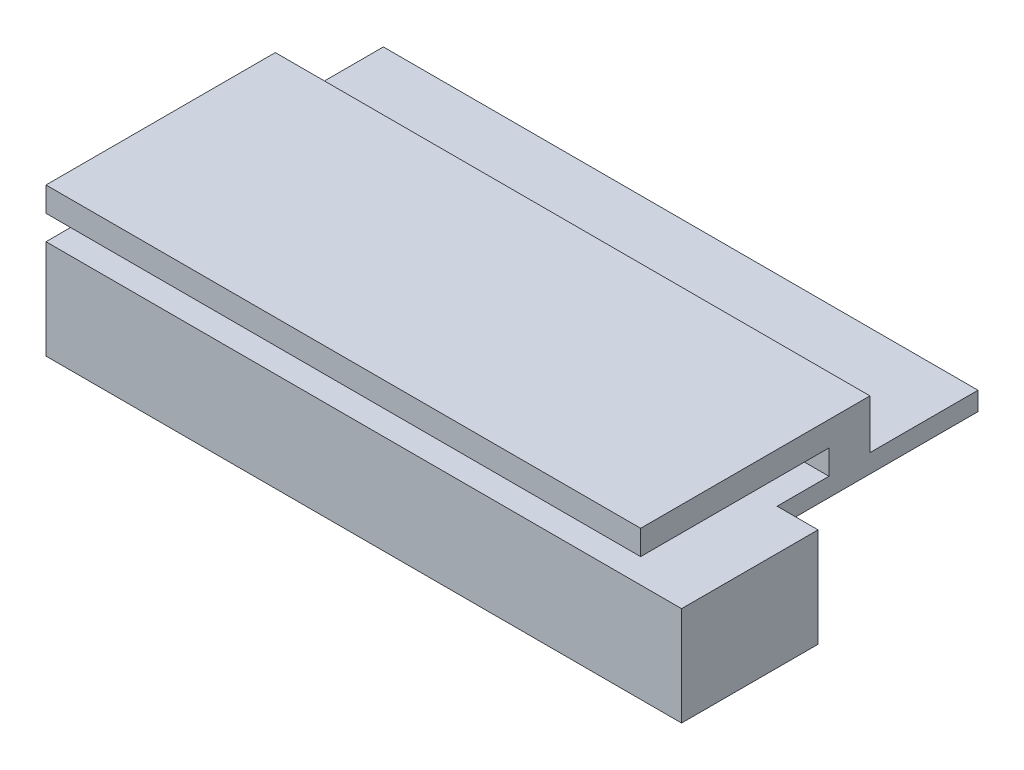
SolidWorks part; units mm, degrees
ref_plane "Front Plane" through (0, 0, 0) normal (0, 0, 1) x (1, 0, 0)
ref_plane "Top Plane" through (0, 0, 0) normal (0, 1, 0) x (1, 0, 0)
ref_plane "Right Plane" through (0, 0, 0) normal (1, 0, 0) x (0, 0, -1)
sketch "Sketch1" plane through (0, 0, 0) normal (0, 1, 0) x (1, 0, 0)
  line L0 (-0.2, 0.2) -> (-0.2, -21.517)
  line L1 (0, 0) -> (40.1638, 0)
  line L2 (0, 0) -> (0, -21.317)
  line L3 (0, -21.317) -> (40.1638, -21.317)
  line L4 (40.1638, 0) -> (40.1638, -21.317)
  line L5 (-0.2, -21.517) -> (40.3637, -21.517)
  line L6 (40.3637, 0.2) -> (40.3637, -21.517)
  line L7 (-0.2, 0.2) -> (40.3637, 0.2)
  line L9 (-0.2, 0.2) -> (-3.2, 0.2)
  line L10 (-0.2, 0.2) -> (-0.2, -21.517)
  line L11 (-0.2, -21.517) -> (-3.2, -21.517)
  line L12 (-3.2, 0.2) -> (-3.2, -21.517)
  line L13 (-3.2, -21.517) -> (40.3637, -21.517)
  line L14 (-3.2, -21.517) -> (-3.2, -24.5169)
  line L15 (-3.2, -24.5169) -> (40.3638, -24.5169)
  line L16 (40.3637, -21.517) -> (40.3638, -24.5169)
  line L17 (40.3638, -24.5169) -> (43.3638, -24.5169)
  line L18 (40.3638, -24.5169) -> (40.3638, -14.5169)
  line L19 (40.3638, -14.5169) -> (43.3638, -14.5169)
  line L20 (43.3638, -24.5169) -> (43.3638, -14.5169)
  line L21 (-0.2, 0.2) -> (2.8, 0.2)
  line L22 (-0.2, 0.2) -> (-0.2, -21.317)
  line L23 (-0.2, -21.317) -> (2.8, -21.317)
  line L24 (2.8, 0.2) -> (2.8, -21.317)
  line L25 (2.8, -18.517) -> (40.3638, -18.517)
  line L26 (2.8, -18.517) -> (2.8, -21.517)
  line L27 (2.8, -21.517) -> (40.3637, -21.517)
  line L28 (40.3638, -18.517) -> (40.3637, -21.517)
  line L29 (37.3638, -18.517) -> (40.3638, -18.517)
  line L30 (37.3638, -18.517) -> (37.3638, -14.5169)
  line L31 (37.3638, -14.5169) -> (40.3638, -14.5169)
  line L32 (40.3638, -18.517) -> (40.3638, -14.5169)
  dimension "D1" = 40.1638
  dimension "D2" = 21.317
  dimension "D4" = 3
  dimension "D5" = 3
  dimension "D6" = 3
  dimension "D7" = 10
  dimension "D8" = 3
  dimension "D9" = 3
  dimension "D10" = 3
  dimension "D3" = 0.2
extrude "Boss-Extrude3" add sketch "Sketch1" against normal blind 1.36 contours L16 L13 L5 L11 L14 L15 | L9 L12 L11 L10 L0 | L24 L1 L2 L3 | L30 L31 L4 L1 L24 L25 | L25 L24 L3 L4 | L31 L30 L25 L4 | L17 L20 L19 L6 L18 L16 | L3 L26 L13 L18 L25 L4 | L4 L31 L6 L7 L24 L1 | L31 L4 L25 L6 | L26 L3 L23 L10 L5 | L24 L7 L0 L23 L2 L1 region at (1.3, 0, -0.1783) region at (-1.7, 0, 10.6585) region at (1.3, 0, 21.417) region at (21.5819, 0, -0.1597) region at (18.5819, 0, 23.017) region at (1.4, 0, 10.6585) region at (21.1975, 0, 9.139) region at (3.1768, 0, 21.4169) region at (21.4819, 0, 19.9169) region at (41.8638, 0, 19.5169) region at (40.2638, 0, 16.517) region at (38.7638, 0, 16.517)
extrude "Boss-Extrude4" add sketch "Sketch1<7>" against normal blind 2.2 from surface contours L24 L1 L2 L3 | L9 L12 L11 L10 L0 | L24 L7 L0 L23 L2 L1 | L26 L3 L23 L10 L5 | L16 L13 L5 L11 L14 L15 | L3 L26 L13 L18 L25 L4 | L25 L24 L3 L4 | L31 L30 L25 L4 | L17 L20 L19 L6 L18 L16 | L31 L4 L25 L6 region at (1.3, 0, -0.1783) region at (-1.7, 0, 10.6585) region at (1.3, 0, 21.417) region at (18.5819, 0, 23.017) region at (1.4, 0, 10.6585) region at (3.1768, 0, 21.4169) region at (21.4819, 0, 19.9169) region at (41.8638, 0, 19.5169) region at (40.2638, 0, 16.517) region at (38.7638, 0, 16.517) starting at face at (26.8425, -1.36, 12.9446)
sketch "Sketch1<7>" plane through (0, 0, 0) normal (0, 1, 0) x (1, 0, 0) same geometry as "Sketch1"
extrude "Boss-Extrude5" add sketch "Sketch1<8>" against normal blind 1.7 from surface contours L9 L12 L11 L10 L0 | L16 L13 L5 L11 L14 L15 | L17 L20 L19 L6 L18 L16 region at (-1.7, 0, 10.6585) region at (18.5819, 0, 23.017) region at (41.8638, 0, 19.5169) starting at face at (20.0819, -3.56, 14.3377)
sketch "Sketch1<8>" plane through (0, 0, 0) normal (0, 1, 0) x (1, 0, 0) same geometry as "Sketch1"
extrude "Boss-Extrude6" add sketch "Sketch1<9>" against normal blind 2 from surface contours L9 L12 L11 L10 L0 | L24 L1 L2 L3 | L16 L13 L5 L11 L14 L15 | L25 L24 L3 L4 | L17 L20 L19 L6 L18 L16 | L31 L30 L25 L4 | L3 L26 L13 L18 L25 L4 | L31 L4 L25 L6 | L26 L3 L23 L10 L5 | L24 L7 L0 L23 L2 L1 region at (1.3, 0, -0.1783) region at (-1.7, 0, 10.6585) region at (1.3, 0, 21.417) region at (18.5819, 0, 23.017) region at (1.4, 0, 10.6585) region at (3.1768, 0, 21.4169) region at (21.4819, 0, 19.9169) region at (41.8638, 0, 19.5169) region at (40.2638, 0, 16.517) region at (38.7638, 0, 16.517) starting at face at (20.0819, -5.26, 15.0877)
sketch "Sketch1<9>" plane through (0, 0, 0) normal (0, 1, 0) x (1, 0, 0) same geometry as "Sketch1"
sketch "Sketch2" plane through (0, 0, 0) normal (0, 1, 0) x (1, 0, 0)
  line L0 (-3.2, 0.2) -> (-3.2, -24.5169) construction
  line L1 (-3.2, -7.7169) -> (40.3637, -7.7169)
  line L2 (-3.2, -7.7169) -> (-3.2, -10.7169)
  line L3 (-3.2, -10.7169) -> (40.3637, -10.7169)
  line L4 (40.3637, -7.7169) -> (40.3637, -10.7169)
  line L6 (-3.2, -24.5169) -> (43.3638, -24.5169) construction
  line L7 (40.3637, 0.2) -> (40.3637, -14.5169) construction
  line L9 (40.3637, -10.7169) -> (-3.2, -10.7169)
  line L10 (40.3637, -10.7169) -> (40.3637, -24.5169)
  line L11 (40.3637, -24.5169) -> (-3.2, -24.5169)
  line L12 (-3.2, -10.7169) -> (-3.2, -24.5169)
  line M5 (40.3637, -14.5169) -> (40.3637, 0.2)
  line M7 (-3.2, 0.2) -> (-3.2, -24.5169)
  line M8 (-3.2, -24.5169) -> (43.3638, -24.5169)
  dimension "D1" = 3
  dimension "D2" = 13.8
extrude "Boss-Extrude7" add sketch "Sketch2" along normal blind 1.8 contours L3 L1 M7 M5 region at (18.5819, 0, 9.2169)
extrude "Boss-Extrude8" add sketch "Sketch2<3>" along normal blind 1.8 from surface contours L10 L3 M5 M7 M8 | L3 L1 M7 M5 region at (18.5819, 0, 9.2169) region at (18.5819, 0, 17.6169) starting at face at (18.5819, 1.8, 9.2169)
sketch "Sketch2<3>" plane through (0, 0, 0) normal (0, 1, 0) x (1, 0, 0) same geometry as "Sketch2"
